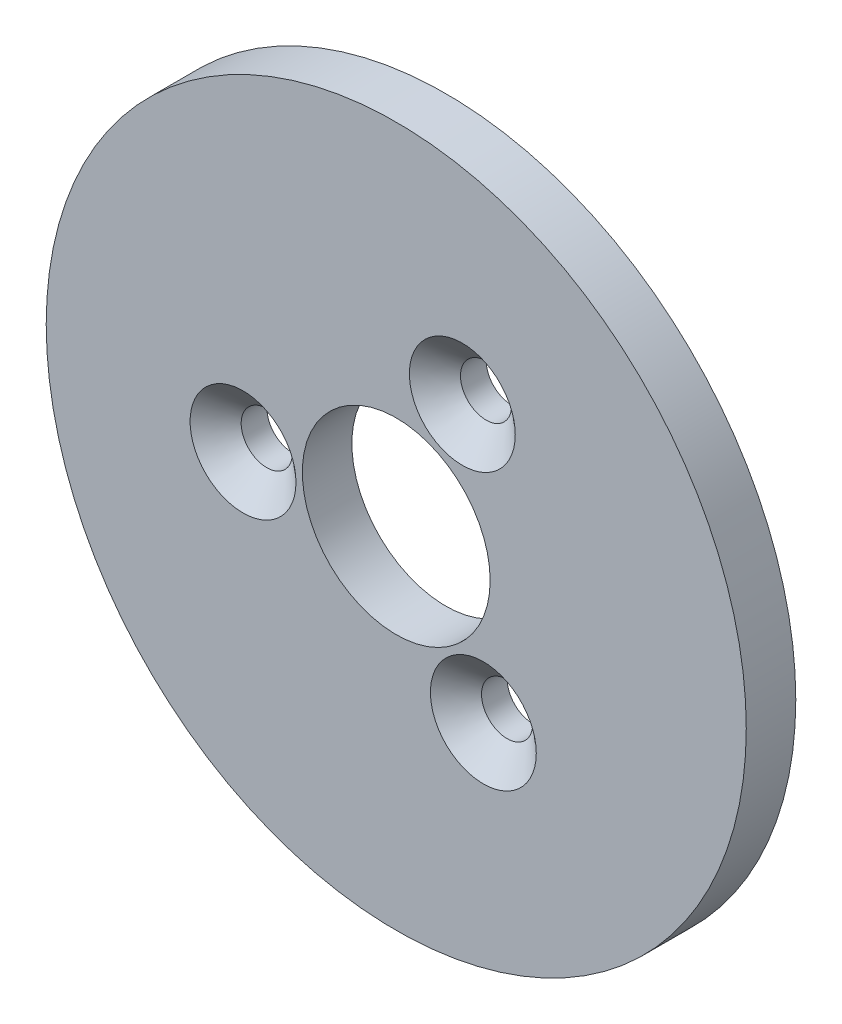
SolidWorks part; units mm, degrees
material "Acrylic (Medium-high impact)"
ref_plane "Front Plane" through (0, 0, 0) normal (0, 0, 1) x (1, 0, 0)
ref_plane "Top Plane" through (0, 0, 0) normal (0, 1, 0) x (1, 0, 0)
ref_plane "Right Plane" through (0, 0, 0) normal (1, 0, 0) x (0, 0, -1)
sketch "Sketch1" plane through (0, 0, 0) normal (0, 0, 1) x (1, 0, 0)
  circle A0 centre (0, 0) radius 20.5
  dimension "D1" = 41
extrude "Boss-Extrude1" add sketch "Sketch1" along normal blind 2.9
sketch "Sketch2" plane through (0, 0, 2.9) normal (0, 0, 1) x (1, 0, 0)
  circle A3 centre (-8.9719, -0.7111) radius 1.5
  circle A4 centre (-8.9719, -0.7111) radius 1.5
  circle A5 centre (5.1018, -7.4143) radius 1.5
  circle A6 centre (5.1018, -7.4143) radius 1.5
  circle A7 centre (3.8701, 8.1254) radius 1.5
  circle A8 centre (3.8701, 8.1254) radius 1.5
  dimension "D2" = 0
  dimension "D3" = 0
  dimension "D4" = 0
extrude "Cut-Extrude1" cut sketch "Sketch2" against normal through all
chamfer "Chamfer1" distance 1.6 angle 41 3 edges at (-7.4719, -0.7111, 2.9) (5.3701, 8.1254, 2.9) (6.6018, -7.4143, 2.9) first distance on face at (6.6018, -7.4143, 2.9)
sketch "Sketch3" plane through (0, 0, 2.9) normal (0, 0, 1) x (1, 0, 0)
  circle A1 centre (0, 0) radius 5.5
  circle A2 centre (0, 0) radius 5.5
  dimension "D1" = 0
extrude "Cut-Extrude2" cut sketch "Sketch3" against normal through all
equation "\"smallPulleyTeeth\"= 15"
equation "\"largePulleyTeeth\"= 30"
equation "\"eighthThick\"= 2.9mm"
equation "\"sixteenthThick\" = 1.7mm"
equation "\"quarterThick\"=6.0mm"
equation "\"OD\" = 146mm"
equation "\"puckAngle\" = 60.5deg"
equation "\"puckDiam\" = 76.5mm"
equation "\"axlePress\" = 5.9mm"
equation "\"press\" = 0.2mm"
equation "\"wheelClear\" = 0.3mm"
equation "\"10-32clear\" = 4.8mm"
equation "\"D1@Boss-Extrude1\"=\"eighthThick\""
equation "\"D1@Chamfer1\"=(6.5-\"6-32clear\")/2"
equation "\"6-32clear\" = 3.3mm"
equation "\"8-32clear\" = 4.0mm"
